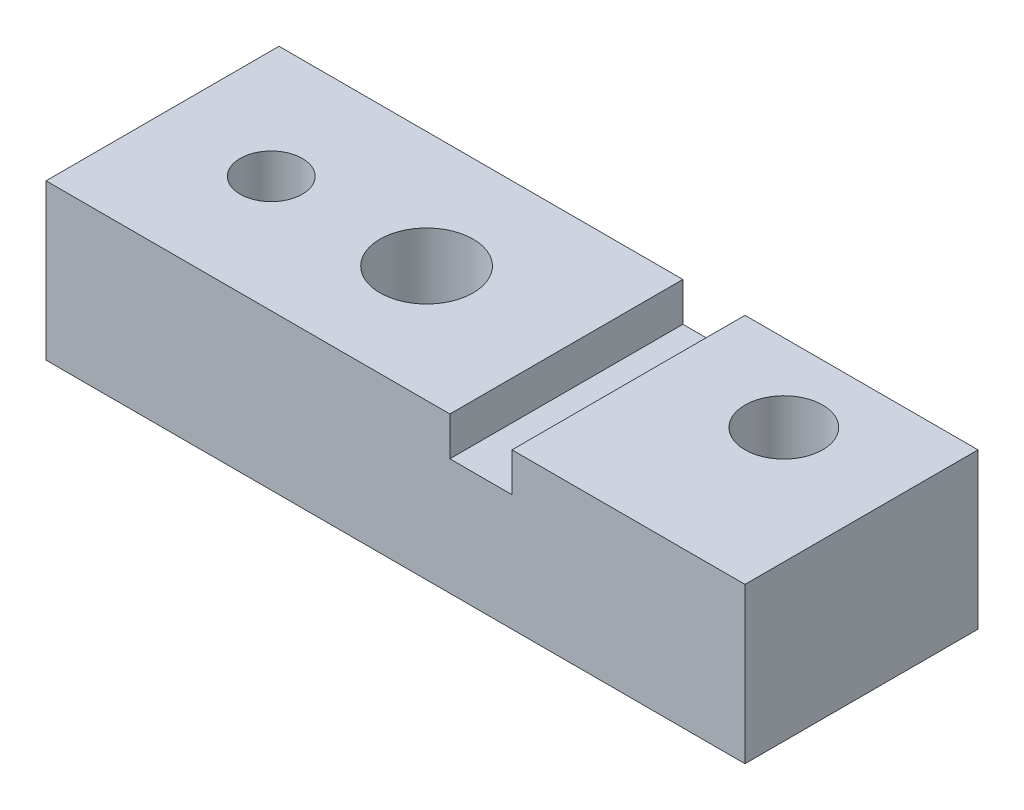
SolidWorks part; units mm, degrees
ref_plane "Спереди" through (0, 0, 0) normal (0, 0, 1) x (1, 0, 0)
ref_plane "Сверху" through (0, 0, 0) normal (0, 1, 0) x (1, 0, 0)
ref_plane "Справа" through (0, 0, 0) normal (1, 0, 0) x (0, 0, -1)
sketch "Эскиз1" plane through (0, 0, 0) normal (0, 1, 0) x (1, 0, 0)
  line L1 (0, 0) -> (90, 0)
  line L2 (0, 0) -> (0, 30)
  line L3 (0, 30) -> (90, 30)
  line L4 (90, 0) -> (90, 30)
  dimension "D1" = 90
  dimension "D2" = 30
extrude "Бобышка-Вытянуть1" add sketch "Эскиз1" against normal blind 20
sketch "Эскиз2" plane through (0, 0, 0) normal (0, 1, 0) x (1, 0, 0)
  line L0 (0, 15) -> (90, 15) construction
  line L1 (0, 30) -> (0, 0) construction
  line L2 (90, 0) -> (90, 30) construction
  line L3 (90, 30) -> (0, 30) construction
  line L4 (52, 30) -> (60, 30)
  line L5 (52, 30) -> (52, 0)
  line L6 (52, 0) -> (60, 0)
  line L7 (60, 30) -> (60, 0)
  line L8 (0, 0) -> (90, 0) construction
  dimension "D1" = 8
  dimension "D2" = 52
extrude "Вырез-Вытянуть1" cut sketch "Эскиз2" against normal blind 5 contours L5 L4 L7 L6
ref_plane "Плоскость4" through (0, 0, -15) normal (0, 0, 1) x (1, 0, 0)
sketch "Эскиз5" plane through (0, 0, -15) normal (0, 0, 1) x (1, 0, 0)
  line L0 (52, 0) -> (52, -29.9124) construction
  line L1 (34, 0) -> (34, -20) construction
  line L2 (0, 0) -> (52, 0) construction
  line L3 (0, -20) -> (90, -20) construction
  line L6 (34, 0) -> (28, 0)
  line L7 (28, 0) -> (28, -12)
  line L8 (28, -12) -> (31, -12)
  line L9 (31, -12) -> (31, -20)
  line L10 (31, -20) -> (34, -20)
  line L11 (34, -20) -> (34, 0)
  dimension "D1" = 18
  dimension "D3" = 6
  dimension "D4" = 12
  dimension "D5" = 3
revolve "Вырез-Повернуть1" cut sketch "Эскиз5" angle 360 about L11
sketch "Эскиз7" plane through (0, 0, -15) normal (0, 0, 1) x (1, 0, 0)
  line L0 (14, 0) -> (14, -20) construction
  line L1 (0, 0) -> (52, 0) construction
  line L2 (0, -20) -> (90, -20) construction
  line L3 (0, -20) -> (0, 0) construction
  line L4 (14, 0) -> (10, 0)
  line L5 (10, 0) -> (10, -10)
  line L6 (10, -10) -> (14, -12.3094)
  line L7 (14, -12.3094) -> (14, 0)
  dimension "D1" = 14
  dimension "D2" = 10
  dimension "D3" = 4
  dimension "D4" = 60
revolve "Вырез-Повернуть2" cut sketch "Эскиз7" angle 360 about L0
sketch "Эскиз8" plane through (0, 0, 0) normal (0, 1, 0) x (1, 0, 0)
  line L0 (60, 15) -> (90, 15) construction
  line L1 (60, 30) -> (60, 0) construction
  line L2 (90, 0) -> (90, 30) construction
  line L3 (60, 0) -> (90, 0) construction
  circle A0 centre (75, 20) radius 5
  dimension "D1" = 15
  dimension "D2" = 20
extrude "Вырез-Вытянуть2" cut sketch "Эскиз8" against normal through all
